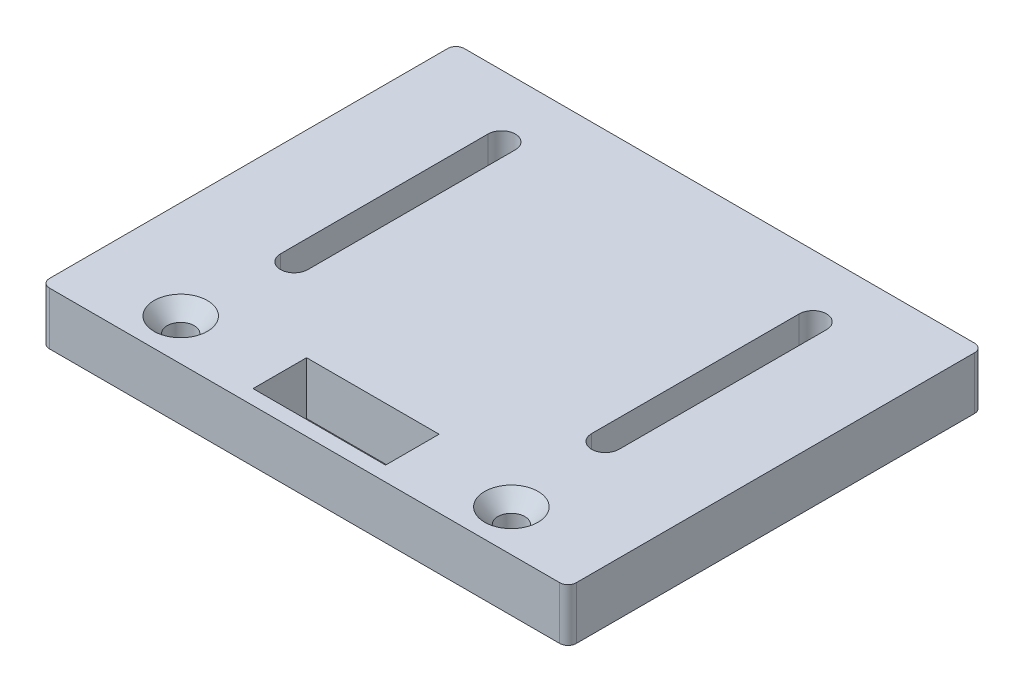
SolidWorks part; units mm, degrees
ref_plane "前基準面" through (0, 0, 0) normal (0, 0, 1) x (1, 0, 0)
ref_plane "上基準面" through (0, 0, 0) normal (0, 1, 0) x (1, 0, 0)
ref_plane "右基準面" through (0, 0, 0) normal (1, 0, 0) x (0, 0, -1)
sketch "Sketch1" plane through (0, 0, 0) normal (0, 1, 0) x (1, 0, 0)
  line L1 (0, 0) -> (127, 0)
  line L2 (0, 0) -> (0, 100)
  line L3 (0, 100) -> (127, 100)
  line L4 (127, 0) -> (127, 100)
extrude "Boss-Extrude1" add sketch "Sketch1" along normal blind 12.7
sketch "Sketch2" plane through (0, 12.7, 0) normal (0, 1, 0) x (1, 0, 0)
  line L6 (47.53, 10) -> (47.53, 16.45)
  line L7 (47.53, 16.45) -> (79.48, 16.45)
  line L8 (79.48, 10) -> (79.48, 16.45)
  line L9 (47.53, 10) -> (47.53, 3.55)
  line L10 (47.53, 3.55) -> (79.48, 3.55)
  line L11 (79.48, 3.55) -> (79.48, 10)
  dimension "D1" = 31.95
  dimension "D2" = 12.9
extrude "Cut-Extrude1" cut sketch "Sketch2" against normal blind 12.7
sketch "Sketch4" plane through (0, 12.7, 0) normal (0, 1, 0) x (1, 0, 0)
  point P7 (23.65, 9.9969)
  point P8 (103.35, 9.9969)
sketch "Sketch6" plane through (0, 12.7, 0) normal (0, 1, 0) x (1, 0, 0)
  line L1 (22.7, 35) -> (22.7, 85)
  line L2 (29.3, 35) -> (29.3, 85)
  line L13 (97.7213, 34.9792) -> (97.7517, 84.9792)
  line L14 (104.3213, 34.9752) -> (104.3517, 84.9752)
  arc A6 (22.7, 35) -> (29.3, 35) centre (26, 35) ccw
  arc A11 (29.3, 85) -> (22.7, 85) centre (26, 85) ccw
  arc A12 (97.7517, 84.9792) -> (104.3517, 84.9752) centre (101.0517, 84.9772) cw
  arc A13 (104.3213, 34.9752) -> (97.7213, 34.9792) centre (101.0213, 34.9772) cw
extrude "Cut-Extrude2" cut sketch "Sketch6" against normal through all
fillet "Fillet1" radius 2 4 edges at (127, 6.35, -100) (127, 6.35, 0) (0, 6.35, 0) (0, 6.35, -100)
hole_wizard "CSK for 1/4 Flat Head Machine Screw1" positions "3DSketch1" profile "Sketch7" countersink size "1/4" standard "ANSI Inch" end condition through all
sketch3d "3DSketch1"
  point P0 (23.65, 12.7, -9.9969)
  point P3 (103.35, 12.7, -9.9969)
sketch "Sketch7" plane through (23.65, 12.7, -9.9969) normal (1, 0, 0) x (0, 0, 1)
  line L0 (0, 0) -> (0, 12.7)
  line L1 (0, 12.7) -> (3.2639, 12.7)
  line L2 (3.2639, 12.7) -> (3.2639, 3.6524)
  line L3 (3.2639, 3.6524) -> (6.4389, 0)
  line L5 (6.4389, 0) -> (0, 0)
  line L6 (-3.2639, 3.6524) -> (-6.4389, 0) construction
  line L11 (0, -6.35) -> (0, 107.95) construction
  dimension "Thru Hole Dia." = 6.5278
  dimension "Thru Hole Depth" = 12.7
  dimension "Near C'Sink Dia." = 12.8778
  dimension "Near C'Sink Angle" = 82
sketch "Sketch8" plane through (0, 12.7, 0) normal (0, 1, 0) x (1, 0, 0)
  point P4 (63.505, 10)
